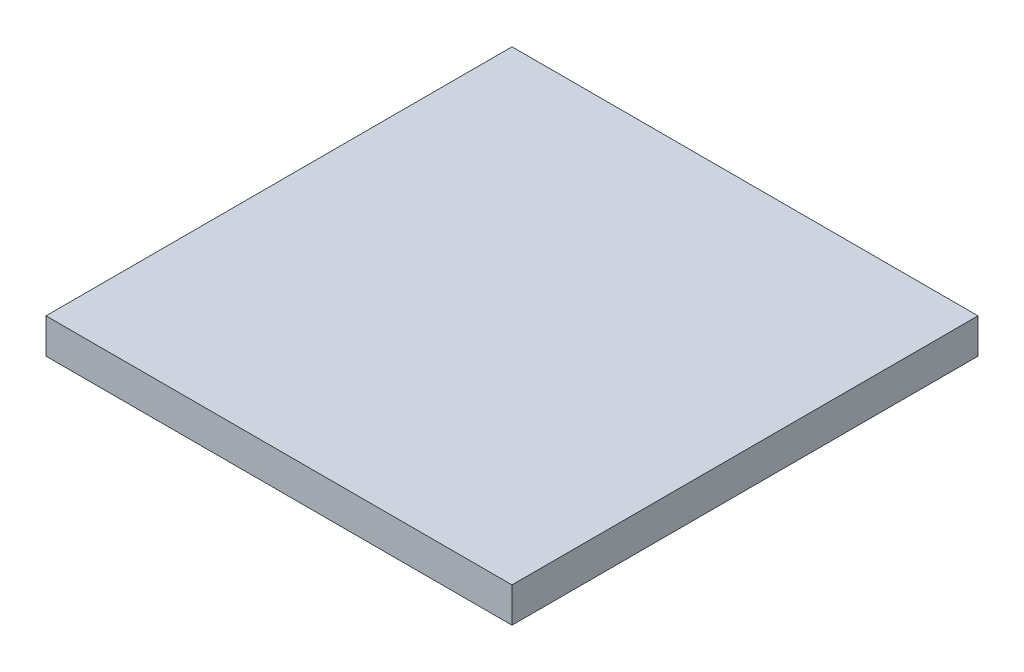
SolidWorks part; units mm, degrees
ref_plane "Front Plane" through (0, 0, 0) normal (0, 0, 1) x (1, 0, 0)
ref_plane "Top Plane" through (0, 0, 0) normal (0, 1, 0) x (1, 0, 0)
ref_plane "Right Plane" through (0, 0, 0) normal (1, 0, 0) x (0, 0, -1)
sketch "Sketch1" plane through (0, 0, 0) normal (0, 1, 0) x (1, 0, 0)
  line L1 (-40, -40) -> (40, -40)
  line L2 (-40, -40) -> (-40, 40)
  line L3 (-40, 40) -> (40, 40)
  line L4 (40, -40) -> (40, 40)
  line L5 (-40, -40) -> (40, 40) construction
  line L6 (-40, 40) -> (40, -40) construction
  point P1 (0, 0)
  dimension "D1" = 80
  dimension "D2" = 80
extrude "Boss-Extrude1" add sketch "Sketch1" along normal blind 6
